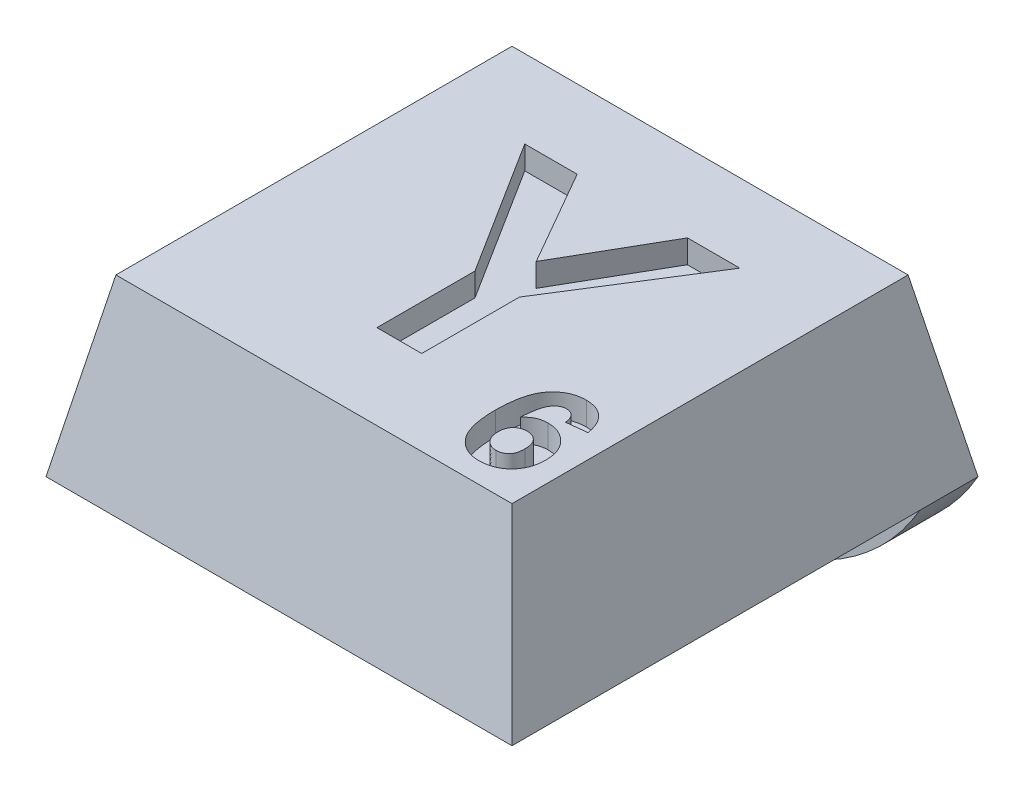
SolidWorks part; units mm, degrees
ref_plane "Front Plane" through (0, 0, 0) normal (0, 0, 1) x (1, 0, 0)
ref_plane "Top Plane" through (0, 0, 0) normal (0, 1, 0) x (1, 0, 0)
ref_plane "Right Plane" through (0, 0, 0) normal (1, 0, 0) x (0, 0, -1)
sketch "Sketch1" plane through (0, 0, 0) normal (0, 1, 0) x (1, 0, 0)
  line L1 (0, 0) -> (8, 0)
  line L2 (0, 0) -> (0, 8)
  line L3 (0, 8) -> (8, 8)
  line L4 (8, 0) -> (8, 8)
  dimension "D1" = 8
  dimension "D2" = 8
extrude "Boss-Extrude1" add sketch "Sketch1" along normal blind 3
sketch "Sketch2" plane through (0, 0, 0) normal (0, 0, 1) x (1, 0, 0)
  line L0 (0, 0) -> (0.6, 3)
  line L1 (0, 3) -> (8, 3) construction
  line L2 (0.6, 3) -> (0, 3)
  line L3 (0, 3) -> (0, 0)
  line L4 (8, 0) -> (7.4, 3)
  line L5 (7.4, 3) -> (8, 3)
  line L6 (8, 3) -> (8, 0)
  dimension "D1" = 0.6
  dimension "D2" = 0.6
extrude "Cut-Extrude1" cut sketch "Sketch2" against normal through all both and the other way through all
sketch "Sketch3" plane through (0, 0, 0) normal (1, 0, 0) x (0, 0, -1)
  line L0 (0, 0) -> (0.6, 3)
  line L1 (8, 3) -> (0, 3) construction
  line L2 (0.6, 3) -> (0, 3)
  line L3 (0, 3) -> (0, 0)
  line L4 (8, 3) -> (7.4, 3)
  line L5 (7.4, 3) -> (8, 0)
  line L6 (8, 3) -> (8, 0)
  dimension "D1" = 0.6
  dimension "D2" = 0.6
extrude "Cut-Extrude2" cut sketch "Sketch3" along normal blind 11
sketch "Sketch4" plane through (0, 0, 0) normal (0, -1, 0) x (1, 0, 0)
  line L0 (8, 0) -> (8, -8) construction
  line L3 (0, 0) -> (8, 0) construction
  circle A0 centre (4, -3.75) radius 1.8
  dimension "D1" = 3.6
  dimension "D2" = 4
  dimension "D3" = 3.75
extrude "Cut-Extrude3" cut sketch "Sketch4" against normal blind 0.8
sketch "Sketch5" plane through (0, 0, 0) normal (0, -1, 0) x (1, 0, 0)
  line L0 (8, 0) -> (8, -8) construction
  line L1 (0, -8) -> (8, -8)
  line L2 (0, -8) -> (0, -7)
  line L3 (0, -7) -> (8, -7)
  line L4 (8, -8) -> (8, -7)
  dimension "D1" = 1
extrude "Boss-Extrude2" add sketch "Sketch5" along normal blind 2
fillet "Fillet1" radius 4 2 edges at (8, -2, -7.5) (0, -2, -7.5)
sketch "Sketch6" plane through (0, 3, 0) normal (0, 1, 0) x (1, 0, 0)
  text T0 "Y" font "Arial" height 4
extrude "Cut-Extrude4" cut sketch "Sketch6" against normal blind 0.4
sketch "Sketch7" plane through (0, 3, 0) normal (0, 1, 0) x (1, 0, 0)
  text T0 "6" font "Arial" height 1.8
extrude "Cut-Extrude5" cut sketch "Sketch7" against normal blind 0.4
